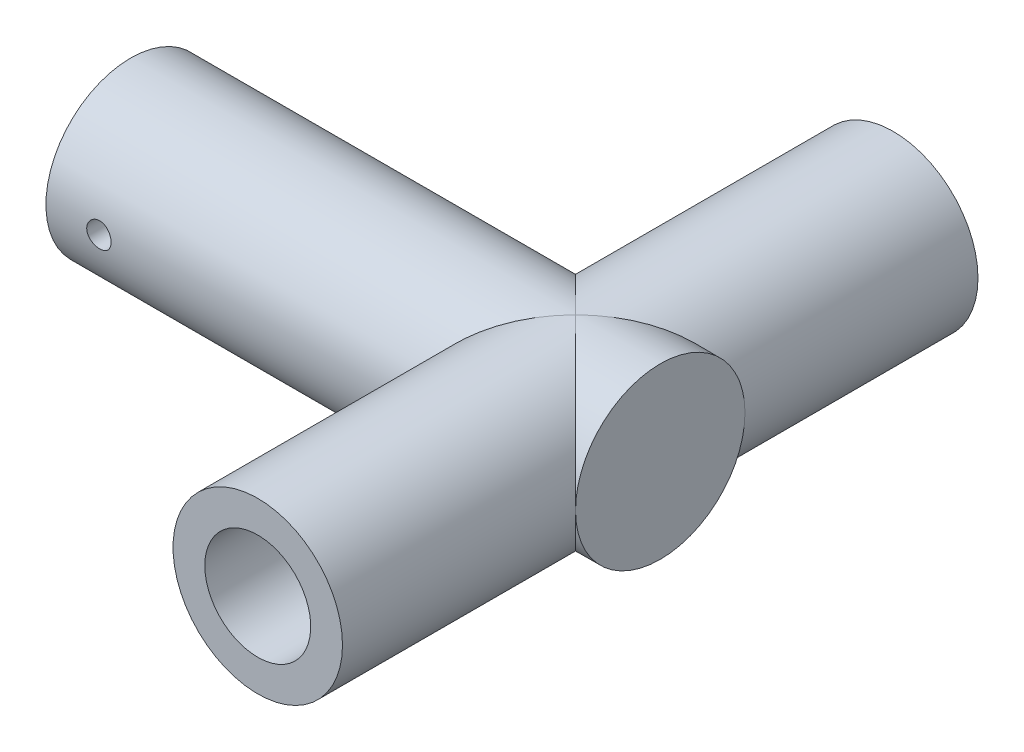
SolidWorks part; units mm, degrees
ref_plane "前视基准面" through (0, 0, 0) normal (0, 0, 1) x (1, 0, 0)
ref_plane "上视基准面" through (0, 0, 0) normal (0, 1, 0) x (1, 0, 0)
ref_plane "右视基准面" through (0, 0, 0) normal (1, 0, 0) x (0, 0, -1)
sketch "草图2" plane through (0, 0, 0) normal (1, 0, 0) x (0, 0, -1)
  circle A0 centre (0, 0) radius 8
extrude "凸台-拉伸1" add sketch "草图2" along normal blind 50
sketch "草图3" plane through (0, 0, 0) normal (-1, 0, 0) x (0, 0, 1)
  circle A0 centre (0, 0) radius 4
extrude "切除-拉伸1" cut sketch "草图3" against normal blind 40
sketch "草图4" plane through (0, 0, 0) normal (0, 0, 1) x (1, 0, 0)
  line L0 (0, 0) -> (5, 0) construction
  circle A0 centre (5, 0) radius 1.15
extrude "切除-拉伸2" cut sketch "草图4" against normal through all and the other way through all
sketch "草图5" plane through (0, 0, 0) normal (0, 0, 1) x (1, 0, 0)
  line L0 (50, -8) -> (50, 8) construction
  line L1 (50, -8) -> (50, 8) construction
  circle A0 centre (42, 0) radius 8
extrude "凸台-拉伸2" add sketch "草图5" along normal blind 30 and the other way blind 30
sketch "草图6" plane through (0, 0, -30) normal (0, 0, -1) x (-1, 0, 0)
  circle A0 centre (-42, 0) radius 5
extrude "切除-拉伸4" cut sketch "草图6" against normal through all contours A0
